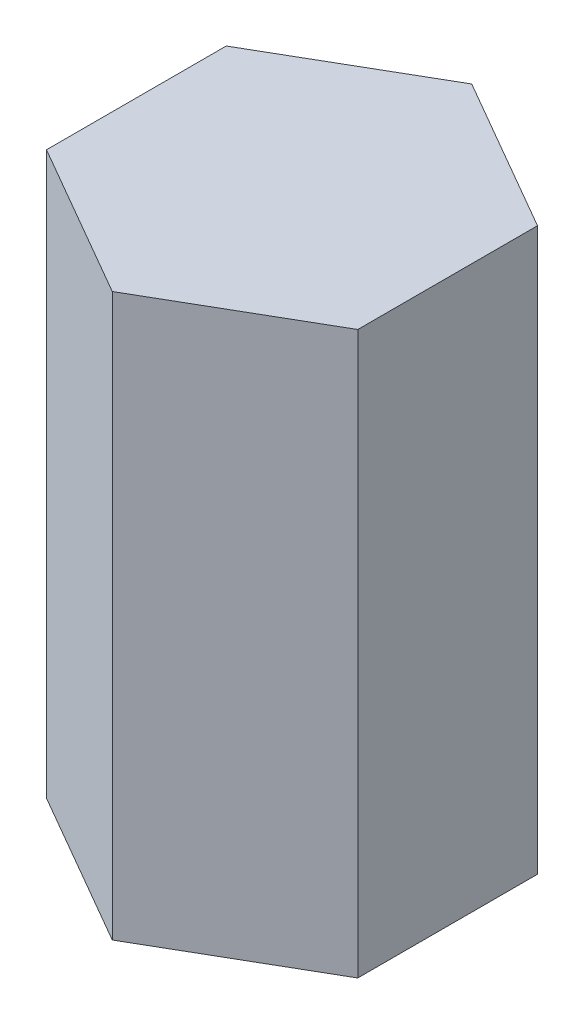
SolidWorks part; units mm, degrees
ref_plane "Front Plane" through (0, 0, 0) normal (0, 0, 1) x (1, 0, 0)
ref_plane "Top Plane" through (0, 0, 0) normal (0, 1, 0) x (1, 0, 0)
ref_plane "Right Plane" through (0, 0, 0) normal (1, 0, 0) x (0, 0, -1)
sketch "Sketch1" plane through (0, 0, 0) normal (0, 1, 0) x (1, 0, 0)
  line L0 (2, -1.8589) -> (2, 1.8589)
  line L8 (-5.2793, -3.048) -> (0, -6.096)
  line L9 (0, -6.096) -> (5.2793, -3.048)
  line L10 (5.2793, -3.048) -> (5.2793, 3.048)
  line L11 (5.2793, 3.048) -> (0, 6.096)
  line L12 (0, 6.096) -> (-5.2793, 3.048)
  line L13 (-5.2793, 3.048) -> (-5.2793, -3.048)
  arc A1 (2, 1.8589) -> (2, -1.8589) centre (0, 0) ccw
  circle A2 centre (0, 0) radius 6.096 construction
  dimension "D1" = 12.192
  dimension "D2" = 5.461
  dimension "D3" = 2
extrude "Boss-Extrude1" add sketch "Sketch1" along normal blind 19.05 contours L12 L13 L8 L9 L10 L11 A1 L0 | L0 A1
extrude "Cut-Extrude1" cut sketch "Sketch1<3>" along normal blind 10.16 contours A1 L0
sketch "Sketch1<3>" plane through (0, 0, 0) normal (0, 1, 0) x (1, 0, 0) same geometry as "Sketch1"
